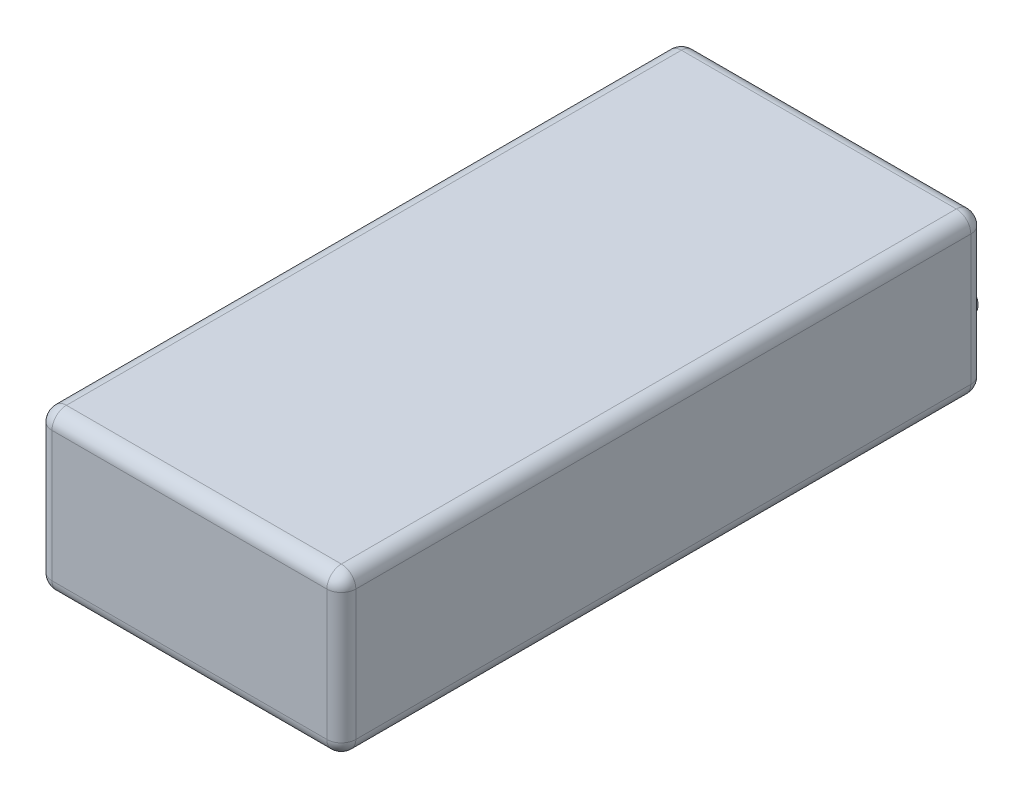
SolidWorks part; units mm, degrees
ref_plane "Спереди" through (0, 0, 0) normal (0, 0, 1) x (1, 0, 0)
ref_plane "Сверху" through (0, 0, 0) normal (0, 1, 0) x (1, 0, 0)
ref_plane "Справа" through (0, 0, 0) normal (1, 0, 0) x (0, 0, -1)
sketch "Эскиз1" plane through (0, 0, 0) normal (0, 1, 0) x (1, 0, 0)
  line L1 (-21, -44.5) -> (21, -44.5)
  line L2 (-21, -44.5) -> (-21, 44.5)
  line L3 (-21, 44.5) -> (21, 44.5)
  line L4 (21, -44.5) -> (21, 44.5)
  line L5 (-21, -44.5) -> (21, 44.5) construction
  line L6 (-21, 44.5) -> (21, -44.5) construction
  point P0 (0, 0)
  dimension "D1" = 42
  dimension "D2" = 89
extrude "тело" add sketch "Эскиз1" along normal blind 11 and the other way blind 11
sketch "Эскиз2" plane through (0, 0, -44.5) normal (0, 0, -1) x (-1, 0, 0)
  line L0 (-21, 11) -> (21, 11) construction
  line L1 (5.5, -1.5) -> (12.5, -1.5)
  line L2 (5.5, -1.5) -> (5.5, 3.5)
  line L3 (5.5, 3.5) -> (12.5, 3.5)
  line L4 (12.5, -1.5) -> (12.5, 3.5)
  line L5 (5.5, -1.5) -> (12.5, 3.5) construction
  line L6 (5.5, 3.5) -> (12.5, -1.5) construction
  line L7 (21, -11) -> (21, 11) construction
  point P0 (9, 1)
  dimension "D1" = 7
  dimension "D2" = 5
  dimension "D3" = 10
  dimension "D4" = 12
extrude "переключатель" add sketch "Эскиз2" along normal blind 2
sketch "Эскиз3" plane through (0, 0, -44.5) normal (0, 0, -1) x (-1, 0, 0)
  line L0 (-21, -11) -> (21, -11) construction
  line L1 (-21, -11) -> (-21, 11) construction
  circle A0 centre (-13, -6) radius 2
  dimension "D1" = 4
  dimension "D2" = 5
  dimension "D3" = 8
extrude "провода" add sketch "Эскиз3" along normal blind 5
sketch "Эскиз4" plane through (0, -11, 0) normal (0, -1, 0) x (1, 0, 0)
  line L0 (21, -44.5) -> (-21, -44.5) construction
  line L1 (-12, 25.5) -> (12, 25.5) construction
  line L2 (-12, 25.5) -> (-12, -14.5) construction
  line L3 (-12, -14.5) -> (12, -14.5) construction
  line L4 (12, 25.5) -> (12, -14.5) construction
  line L5 (-12, 25.5) -> (12, -14.5) construction
  line L6 (-12, -14.5) -> (12, 25.5) construction
  circle A0 centre (-12, 25.5) radius 2.5
  circle A1 centre (12, 25.5) radius 2.5
  circle A2 centre (12, -14.5) radius 2.5
  circle A3 centre (-12, -14.5) radius 2.5
  point P0 (0, 5.5)
  dimension "D1" = 5
  dimension "D2" = 30
  dimension "D3" = 40
  dimension "D4" = 24
extrude "крепежные отверстия" cut sketch "Эскиз4" against normal blind 10
fillet "Скругление1" radius 2 12 edges at (0, -11, -44.5) (-21, -11, 0) (-21, 0, -44.5) (21, -11, 0) (21, 0, -44.5) (0, -11, 44.5) (-21, 0, 44.5) (21, 0, 44.5) (0, 11, 44.5) (-21, 11, 0) (0, 11, -44.5) (21, 11, 0)
